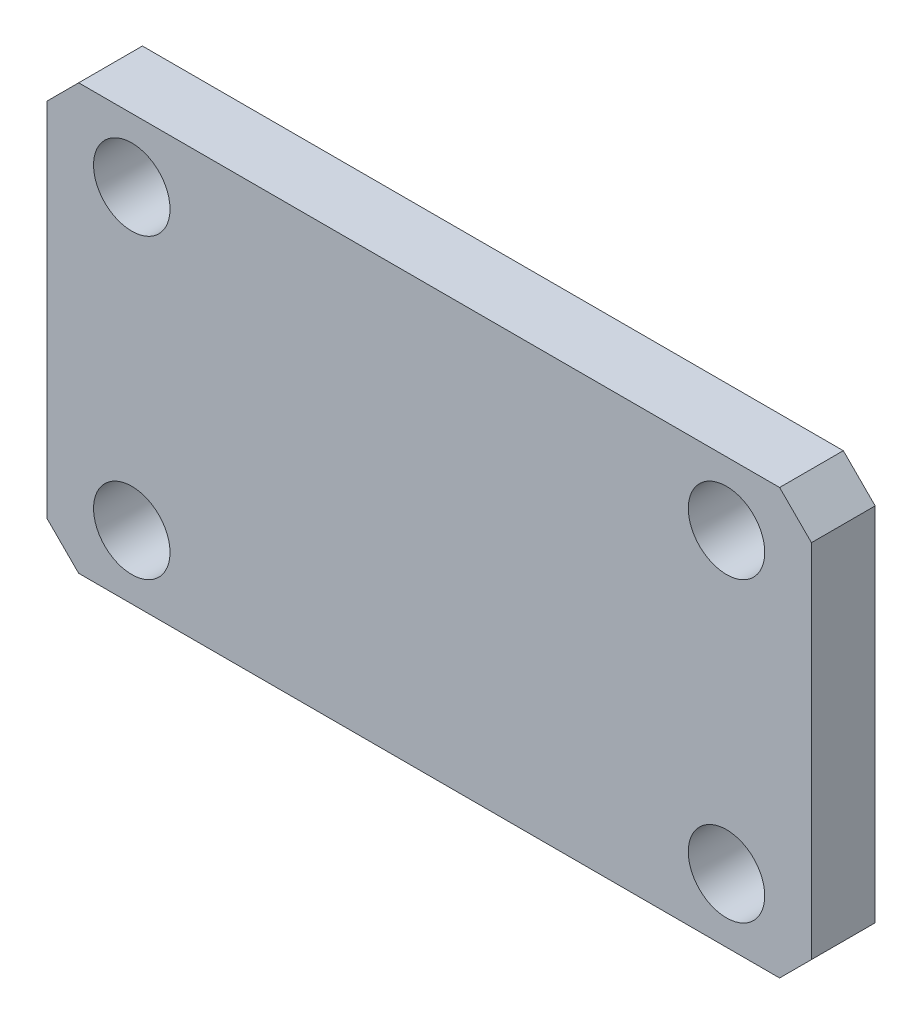
SolidWorks part; units mm, degrees
material "PETG"
ref_plane "Płaszczyzna przednia" through (0, 0, 0) normal (0, 0, 1) x (1, 0, 0)
ref_plane "Płaszczyzna górna" through (0, 0, 0) normal (0, 1, 0) x (1, 0, 0)
ref_plane "Płaszczyzna prawa" through (0, 0, 0) normal (1, 0, 0) x (0, 0, -1)
sketch "Sketch1" plane through (0, 0, 0) normal (0, 0, 1) x (1, 0, 0)
  line L1 (0, 0) -> (36, 0)
  line L2 (0, 0) -> (0, 20)
  line L3 (0, 20) -> (36, 20)
  line L4 (36, 0) -> (36, 20)
  dimension "D1" = 20
  dimension "D2" = 36
extrude "Boss-Extrude1" add sketch "Sketch1" along normal blind 3
hole_wizard "M3 Clearance Hole1" positions "Sketch2" profile "Sketch3" hole size "M3" standard "DIN"
sketch "Sketch2" plane through (0, 0, 3) normal (0, 0, 1) x (1, 0, 0)
  line L0 (4, 3) -> (32, 17) construction
  line L2 (32, 3) -> (4, 17) construction
  line L4 (18, 10) -> (18, 0) construction
  line L5 (0, 0) -> (36, 0) construction
  line L7 (18, 10) -> (36, 10) construction
  line L8 (36, 0) -> (36, 20) construction
  point P0 (4, 17)
  point P6 (32, 17)
  point P7 (32, 3)
  point P8 (4, 3)
  dimension "D3" = 14
  dimension "D4" = 28
  dimension "D1" = 2
  dimension "D2" = 2
sketch "Sketch3" plane through (4, 17, 3) normal (1, 0, 0) x (0, -1, 0)
  line L0 (0, 0) -> (0, 11.0815)
  line L1 (0, 11.0815) -> (1.8, 10)
  line L2 (1.8, 10) -> (1.8, 0)
  line L5 (1.8, 0) -> (0, 0)
  line L10 (0, 11.0815) -> (-1.8, 10) construction
  line L11 (0, -6.35) -> (0, 107.95) construction
  dimension "Hole Dia." = 3.6
  dimension "Hole Depth" = 10
  dimension "Drill Angle" = 118
chamfer "Chamfer1" distance 1.5 angle 45 4 edges at (36, 20, 1.5) (36, 0, 1.5) (0, 0, 1.5) (0, 20, 1.5)
sketch "Sketch4" plane through (0, 0, 0) normal (0, 0, 1) x (1, 0, 0)
  line L0 (18, 20) -> (18, 16) construction
  line L1 (8, 16) -> (28, 16)
  line L2 (8, 16) -> (8, 4)
  line L3 (8, 4) -> (28, 4)
  line L4 (28, 16) -> (28, 4)
  line L5 (34.5, 20) -> (1.5, 20) construction
  line L6 (28, 10) -> (36, 10) construction
  line L7 (36, 1.5) -> (36, 18.5) construction
  dimension "D1" = 12
  dimension "D2" = 20
extrude "Cut-Extrude1" cut sketch "Sketch4" along normal blind 0.5
sketch "Sketch5" plane through (0, 0, 0.5) normal (0, 0, -1) x (-1, 0, 0)
  line L12 (-9, 5) -> (-9, 15)
  line L13 (-9, 15) -> (-27, 15)
  line L14 (-27, 15) -> (-27, 5)
  line L15 (-27, 5) -> (-9, 5)
  line L16 (-8, 4) -> (-8, 16)
  line L17 (-8, 16) -> (-28, 16)
  line L18 (-28, 16) -> (-28, 4)
  line L19 (-28, 4) -> (-8, 4)
  line L20 (-8, 4) -> (-8, 16)
  line L21 (-8, 16) -> (-28, 16)
  line L22 (-28, 16) -> (-28, 4)
  line L23 (-28, 4) -> (-8, 4)
  dimension "D1" = 0
  dimension "D2" = 1
extrude "Boss-Extrude2" add sketch "Sketch5" along normal blind 1 separate body contours L14 L15 L12 L13 region at (18, 10, 0.5)
